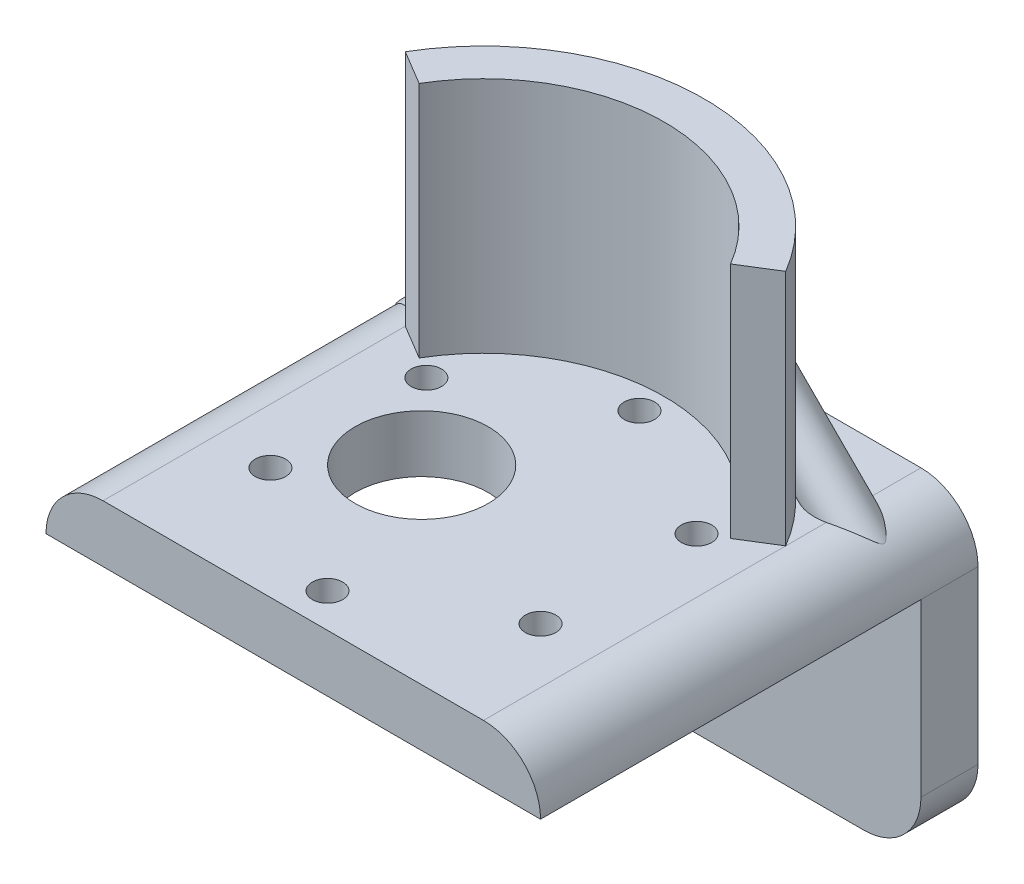
SolidWorks part; units mm, degrees
ref_plane "Front Plane" through (0, 0, 0) normal (0, 0, 1) x (1, 0, 0)
ref_plane "Top Plane" through (0, 0, 0) normal (0, 1, 0) x (1, 0, 0)
ref_plane "Right Plane" through (0, 0, 0) normal (1, 0, 0) x (0, 0, -1)
sketch "Sketch3" plane through (0, 0, 0) normal (0, 0, 1) x (1, 0, 0)
  line L0 (-20, 10.2406) -> (20, 10.2406)
  line L1 (26, 4.2406) -> (26, -13.7594)
  line L2 (20, -19.7594) -> (-20, -19.7594)
  line L3 (0, 19.985) -> (0, -19.985) construction
  line L4 (-26, 4.2406) -> (-26, -13.7594)
  arc A0 (20, 10.2406) -> (26, 4.2406) centre (20, 4.2406) cw
  arc A1 (26, -13.7594) -> (20, -19.7594) centre (20, -13.7594) cw
  arc A2 (-26, -13.7594) -> (-20, -19.7594) centre (-20, -13.7594) ccw
  arc A3 (-20, 10.2406) -> (-26, 4.2406) centre (-20, 4.2406) ccw
  point P12 (0, 0)
  point P14 (0, -19.7594)
  point P19 (0, 10.2406)
  dimension "D3" = 6
  dimension "D4" = 6
  dimension "D1" = 30
  dimension "D2" = 52
extrude "Boss-Extrude1" add sketch "Sketch3" along normal blind 6
sketch "Sketch4" plane through (0, 0, 6) normal (0, 0, 1) x (1, 0, 0)
  line L0 (-26, 4.2406) -> (26, 4.2406)
  line L1 (20, 10.2406) -> (-20, 10.2406)
  arc A0 (26, 4.2406) -> (20, 10.2406) centre (20, 4.2406) ccw
  arc A1 (-20, 10.2406) -> (-26, 4.2406) centre (-20, 4.2406) ccw
extrude "Boss-Extrude2" add sketch "Sketch4" along normal blind 40
sketch "Sketch7" plane through (0, 0, 0) normal (0, 0, -1) x (-1, 0, 0)
  circle A0 centre (0, -4.7594) radius 4
  dimension "D1" = 8
sketch "Sketch9" plane through (0, 10.2406, 0) normal (0, 1, 0) x (1, 0, 0)
  line L0 (20, -46) -> (-20, -46) construction
  circle A0 centre (0, -26) radius 18.5
  circle A1 centre (0, -26) radius 18
  circle A2 centre (0, -9.6) radius 1.6
  circle A3 centre (14.2028, -17.8) radius 1.6
  circle A4 centre (14.2028, -34.2) radius 1.6
  circle A5 centre (0, -42.4) radius 1.6
  circle A6 centre (-14.2028, -34.2) radius 1.6
  circle A7 centre (-14.2028, -17.8) radius 1.6
  point P20 (0, -26)
  dimension "D1" = 37
  dimension "D3" = 36
  dimension "D4" = 3.2
  dimension "D2" = 20
  dimension "D5" = 6
extrude "Cut-Extrude1" cut sketch "Sketch9" against normal up to next contours A5 | A4 | A6 | A7 | A2 | A3 region at (14.2028, 10.2406, 17.8) region at (0, 10.2406, 9.6) region at (-14.2028, 10.2406, 17.8) region at (-14.2028, 10.2406, 34.2) region at (0, 10.2406, 42.4) region at (14.2028, 10.2406, 34.2)
sketch "Sketch10" plane through (0, 10.2406, 0) normal (0, 1, 0) x (1, 0, 0)
  circle A0 centre (-6.5, -26) radius 7
  point P0 (0, -26)
  dimension "D1" = 14
  dimension "D2" = 6.5
extrude "Cut-Extrude2" cut sketch "Sketch10" against normal up to next
sketch "Sketch11" plane through (0, 10.2406, 0) normal (0, 1, 0) x (1, 0, 0)
  line L4 (20, -46) -> (20, 0) construction
  line L5 (-20, -46) -> (-20, 0) construction
  line L7 (20, -14.2178) -> (16.4217, -16.4434)
  line L8 (-20, -14.2178) -> (-16.3838, -16.3787)
  arc A3 (-16.3838, -16.3787) -> (16.4217, -16.4434) centre (0, -26) cw
  arc A4 (20, -14.2178) -> (-20, -14.2178) centre (0, -26) ccw
  dimension "D1" = 19
extrude "Boss-Extrude4" add sketch "Sketch11" along normal blind 25
ref_axis "Axis2" through (26, 10.2406, 0) along (0, 0, 1)
ref_plane "Plane1" through (7.8797, -7.8797, 0) normal (-0.7071, 0.7071, 0) x (0, 0, 1)
ref_axis "Axis3" through (-26, 10.2406, 6) along (0, 0, -1)
ref_plane "Plane2" through (-7.8797, -7.8797, 0) normal (0.7071, 0.7071, 0) x (0, 0, -1)
sketch "Sketch12" plane through (7.8797, -7.8797, 0) normal (-0.7071, 0.7071, 0) x (0, 0, 1)
  circle A0 centre (7.5748, 20.5948) radius 2.5
  dimension "D1" = 5
extrude "Boss-Extrude5" add sketch "Sketch12" along normal up to surface (9.2719 mm away) up to face at (0, 22.7406, 8.5026)
sketch "Sketch14" plane through (-7.8797, -7.8797, 0) normal (0.7071, 0.7071, 0) x (0, 0, -1)
  circle A0 centre (-10.2833, 20.7805) radius 2.5
  dimension "D1" = 5
extrude "Boss-Extrude6" add sketch "Sketch14" along normal up to surface (10.266 mm away) up to face at (0, 22.7406, 8.5026)
sketch "Sketch17" plane through (0, 0, 0) normal (0, 0, -1) x (-1, 0, 0)
  line L0 (-20, 10.2406) -> (20, 10.2406) construction
  line L1 (4.8696, -22.5171) -> (31.8363, -22.5171)
  line L2 (4.8696, -22.5171) -> (4.8696, 4.2406)
  line L3 (4.8696, 4.2406) -> (31.8363, 4.2406)
  line L4 (31.8363, -22.5171) -> (31.8363, 4.2406)
  dimension "D1" = 6
extrude "Cut-Extrude4" cut sketch "Sketch17" against normal up to surface (6 mm away) up to face at (0, -10.1736, 6)
fillet "Fillet1" radius 2 2 edges at (-4.8696, -19.7594, 3) (-4.8696, 4.2406, 3)
extrude "Cut-Extrude5" cut sketch "Sketch7" against normal blind 3
